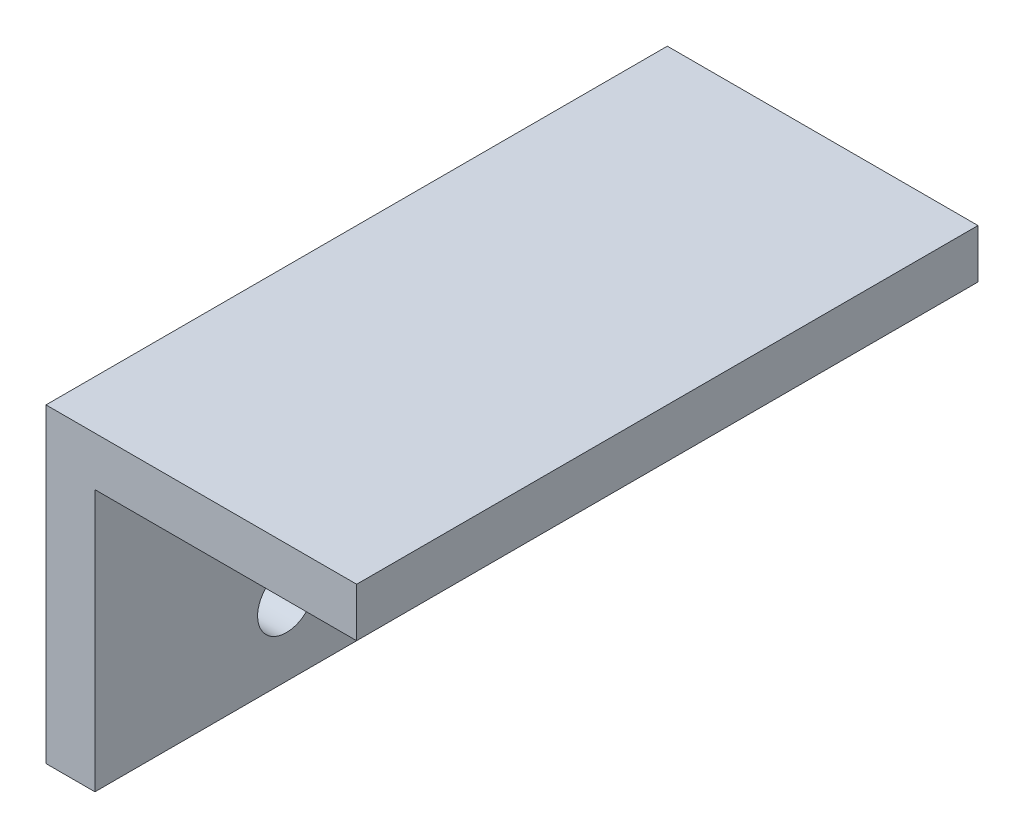
SolidWorks part; units mm, degrees
material "1060 Alloy"
ref_plane "Front Plane" through (0, 0, 0) normal (0, 0, 1) x (1, 0, 0)
ref_plane "Top Plane" through (0, 0, 0) normal (0, 1, 0) x (1, 0, 0)
ref_plane "Right Plane" through (0, 0, 0) normal (1, 0, 0) x (0, 0, -1)
sketch "Sketch1" plane through (0, 0, 0) normal (0, 0, 1) x (1, 0, 0)
  line L0 (0, 0) -> (0, -21.4)
  line L1 (0, -21.4) -> (-4, -21.4)
  line L2 (-4, -21.4) -> (-4, 4)
  line L3 (-4, 4) -> (21.4, 4)
  line L4 (21.4, 4) -> (21.4, 0)
  line L5 (21.4, 0) -> (0, 0)
  dimension "D1" = 25.4
  dimension "D2" = 4
extrude "Boss-Extrude1" add sketch "Sketch1" along normal blind 50.8
sketch "Sketch2" plane through (0, 0, 0) normal (1, 0, 0) x (0, 0, -1)
  line L0 (-35.15, -15.6) -> (-15.65, -15.6) construction
  line L1 (-25.4, -21.4) -> (-25.4, 0) construction
  line L2 (-50.8, -21.4) -> (0, -21.4) construction
  line L3 (-50.8, 0) -> (0, 0) construction
  circle A0 centre (-35.15, -15.6) radius 2.35
  circle A1 centre (-15.65, -15.6) radius 2.35
  point P10 (-25.4, -15.6)
  dimension "D2" = 4.7
  dimension "D1" = 19.5
  dimension "D3" = 5.8
extrude "Cut-Extrude1" cut sketch "Sketch2" against normal through all
